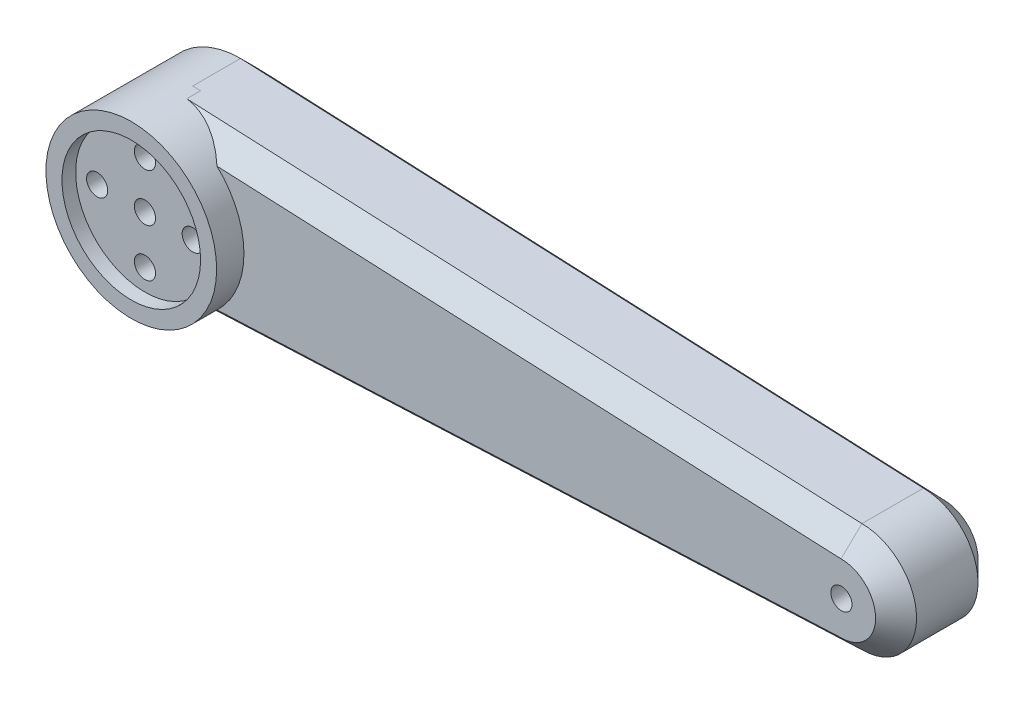
SolidWorks part; units mm, degrees
material "petg 20%"
ref_plane "Front Plane" through (0, 0, 0) normal (0, 0, 1) x (1, 0, 0)
ref_plane "Top Plane" through (0, 0, 0) normal (0, 1, 0) x (1, 0, 0)
ref_plane "Right Plane" through (0, 0, 0) normal (1, 0, 0) x (0, 0, -1)
sketch "Sketch1" plane through (0, 0, 0) normal (0, 0, 1) x (1, 0, 0)
  line L0 (0, 12.5) -> (100, 8)
  line L1 (0, -12.5) -> (100, -8)
  arc A0 (0, 12.5) -> (0, -12.5) centre (0, 0) ccw
  arc A1 (100, -8) -> (100, 8) centre (100, 0) ccw
  dimension "D1" = 25
  dimension "D2" = 16
  dimension "D3" = 100
extrude "Boss-Extrude1" add sketch "Sketch1" along normal blind 17
sketch "Sketch2" plane through (0, 0, 17) normal (0, 0, 1) x (1, 0, 0)
  circle A0 centre (0, 0) radius 12.5
  circle A1 centre (0, 0) radius 10.15
  dimension "D1" = 20.3
sketch "Sketch3" plane through (0, 0, 17) normal (0, 0, 1) x (1, 0, 0)
  circle A0 centre (0, 0) radius 1.55
  circle A1 centre (-7, 0) radius 1.55
  circle A2 centre (0, 7) radius 1.55
  circle A3 centre (7, 0) radius 1.55
  circle A4 centre (0, -7) radius 1.55
  point P14 (0, 0)
  dimension "D1" = 3.1
  dimension "D2" = 3.1
  dimension "D3" = 7
  dimension "D4" = 4
extrude "Cut-Extrude2" cut sketch "Sketch3" against normal through all
sketch "Sketch4" plane through (0, 0, 17) normal (0, 0, 1) x (1, 0, 0)
  circle A0 centre (100, 0) radius 1.55
  dimension "D1" = 3.1
extrude "Cut-Extrude3" cut sketch "Sketch4" against normal through all
sketch "Sketch5" plane through (0, 0, 0) normal (0, 0, -1) x (-1, 0, 0)
  circle A0 centre (0, 0) radius 3
  circle A1 centre (-7, 0) radius 3
  circle A2 centre (0, 7) radius 3
  circle A3 centre (7, 0) radius 3
  circle A4 centre (0, -7) radius 3
  circle A5 centre (-100, 0) radius 3
  point P15 (0, 0)
  dimension "D1" = 6
  dimension "D2" = 6
  dimension "D4" = 6
  dimension "D3" = 4
extrude "Cut-Extrude4" cut sketch "Sketch5" against normal blind 2
chamfer "Chamfer5" distance 3 angle 45 4 edges at (108, 0, 0) (50, -10.25, 0) (-12.5, 0, 0) (50, 10.25, 0)
extrude "Boss-Extrude4" add sketch "Sketch2" against normal blind 7 contours A0 | A1
sketch "Sketch6" plane through (0, 0, 17) normal (0, 0, 1) x (1, 0, 0)
  circle A0 centre (0, 7) radius 1.55
  circle A1 centre (7, 0) radius 1.55
  circle A2 centre (0, 0) radius 1.55
  circle A3 centre (0, -7) radius 1.55
  circle A4 centre (-7, 0) radius 1.55
  circle A5 centre (0, 0) radius 12.5
  circle A6 centre (0, 0) radius 10.15
sketch "Sketch7" plane through (0, 0, 17) normal (0, 0, 1) x (1, 0, 0)
  line L0 (100, 8) -> (0.8739, 12.4694)
  line L1 (0.8739, -12.4694) -> (100, -8)
  arc A0 (0.8739, -12.4694) -> (0.8739, 12.4694) centre (0, 0) ccw
  arc A1 (100, -8) -> (100, 8) centre (100, 0) ccw
extrude "Cut-Extrude5" cut sketch "Sketch7" against normal blind 2
chamfer "Chamfer6" distance 3 angle 45 3 edges at (50.5614, -10.2247, 15) (108, 0, 15) (50.5614, 10.2247, 15)
extrude "Boss-Extrude5" add sketch "Sketch6" along normal blind 2 contours A0 A5 A6 region at (-12.1464, 0, 17)
